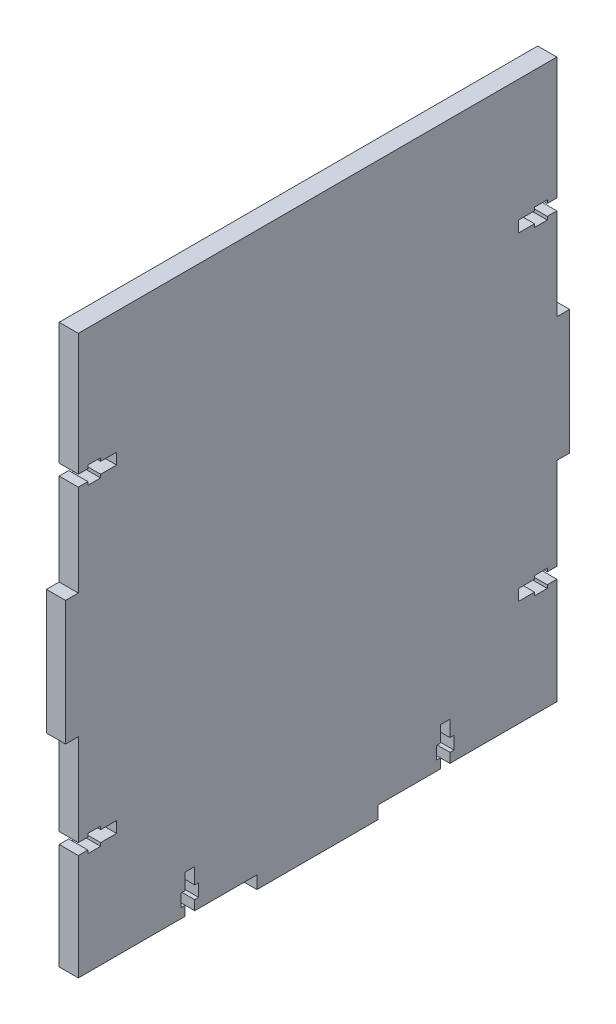
SolidWorks part; units mm, degrees
material "1060 Alloy"
ref_plane "Front Plane" through (0, 0, 0) normal (0, 0, 1) x (1, 0, 0)
ref_plane "Top Plane" through (0, 0, 0) normal (0, 1, 0) x (1, 0, 0)
ref_plane "Right Plane" through (0, 0, 0) normal (1, 0, 0) x (0, 0, -1)
sketch "Sketch1" plane through (0, 0, 0) normal (1, 0, 0) x (0, 0, -1)
  line L1 (-75, 0) -> (75, 0)
  line L2 (-75, 0) -> (-75, -175)
  line L3 (-75, -175) -> (75, -175)
  line L4 (75, 0) -> (75, -175)
  dimension "D1" = 150
  dimension "D2" = 175
sheet metal parameters "Sheet-Metal1" thickness 6 parameters "D1"=5
base flange "Base-Flange1" sketch "Sketch1" thickness 6 reverse thickness direction no parameters "D1"=5
sketch "Sketch4" plane through (0, 0, 0) normal (1, 0, 0) x (0, 0, -1)
  line L0 (-75, -38.25) -> (-75, -41.75)
  line L1 (-75, 0) -> (-75, -175) construction
  line L2 (-75, 0) -> (-75, -175) construction
  line L3 (-75, -41.75) -> (-72, -41.75)
  line L4 (-72, -41.75) -> (-72, -42.75)
  line L5 (-72, -42.75) -> (-68, -42.75)
  line L6 (-68, -42.75) -> (-68, -41.75)
  line L7 (-68, -41.75) -> (-63, -41.75)
  line L8 (-63, -41.75) -> (-63, -38.25)
  line L9 (-63, -38.25) -> (-68, -38.25)
  line L10 (-68, -38.25) -> (-68, -37.25)
  line L11 (-68, -37.25) -> (-72, -37.25)
  line L12 (-72, -37.25) -> (-72, -38.25)
  line L13 (-72, -38.25) -> (-75, -38.25)
  line L14 (-75, -90) -> (75, -90) construction
  line L15 (75, -175) -> (75, 0) construction
  line L16 (0, -90) -> (0, 0) construction
  line L17 (-75, -40) -> (-63, -40) construction
  line L18 (75, 0) -> (-75, 0) construction
  line L19 (-75, -140) -> (-63, -140) construction
  line L20 (-72, -141.75) -> (-75, -141.75)
  line L21 (-72, -142.75) -> (-72, -141.75)
  line L22 (-68, -142.75) -> (-72, -142.75)
  line L23 (-68, -141.75) -> (-68, -142.75)
  line L24 (-63, -141.75) -> (-68, -141.75)
  line L25 (-63, -138.25) -> (-63, -141.75)
  line L26 (-68, -138.25) -> (-63, -138.25)
  line L27 (-68, -137.25) -> (-68, -138.25)
  line L28 (-72, -137.25) -> (-68, -137.25)
  line L29 (-72, -138.25) -> (-72, -137.25)
  line L30 (-75, -138.25) -> (-72, -138.25)
  line L31 (-75, -141.75) -> (-75, -138.25)
  line L32 (75, -140) -> (63, -140) construction
  line L33 (75, -141.75) -> (75, -138.25)
  line L34 (75, -138.25) -> (72, -138.25)
  line L35 (72, -138.25) -> (72, -137.25)
  line L36 (72, -137.25) -> (68, -137.25)
  line L37 (68, -137.25) -> (68, -138.25)
  line L38 (68, -138.25) -> (63, -138.25)
  line L39 (63, -138.25) -> (63, -141.75)
  line L40 (63, -141.75) -> (68, -141.75)
  line L41 (68, -141.75) -> (68, -142.75)
  line L42 (68, -142.75) -> (72, -142.75)
  line L43 (72, -142.75) -> (72, -141.75)
  line L44 (72, -141.75) -> (75, -141.75)
  line L45 (75, -40) -> (63, -40) construction
  line L46 (72, -38.25) -> (75, -38.25)
  line L47 (72, -37.25) -> (72, -38.25)
  line L48 (68, -37.25) -> (72, -37.25)
  line L49 (68, -38.25) -> (68, -37.25)
  line L50 (63, -38.25) -> (68, -38.25)
  line L51 (63, -41.75) -> (63, -38.25)
  line L52 (68, -41.75) -> (63, -41.75)
  line L53 (68, -42.75) -> (68, -41.75)
  line L54 (72, -42.75) -> (68, -42.75)
  line L55 (72, -41.75) -> (72, -42.75)
  line L56 (75, -41.75) -> (72, -41.75)
  line L57 (75, -38.25) -> (75, -41.75)
  dimension "D1" = 3.5
  dimension "D2" = 5.5
  dimension "D3" = 4
  dimension "D4" = 3
  dimension "D5" = 5
  dimension "D6" = 40
  dimension "D7" = 100
extrude "Cut-Extrude1" cut sketch "Sketch4" against normal through all normal cut yes
sketch "Sketch5" plane through (0, 0, 0) normal (1, 0, 0) x (0, 0, -1)
  line L0 (-75, -38.25) -> (-75, -41.75) construction
  line L1 (-75, -138.25) -> (-75, -141.75) construction
  line L2 (-75, -140) -> (-75, -40) construction
  line L3 (-75, -90) -> (-79, -90) construction
  line L4 (0, 0) -> (0, -175) construction
  line L5 (-79, -70.5) -> (-75, -70.5)
  line L6 (-79, -70.5) -> (-79, -109.5)
  line L7 (-79, -109.5) -> (-75, -109.5)
  line L8 (-75, -70.5) -> (-75, -109.5)
  line L9 (-75, -175) -> (75, -175) construction
  line L10 (75, -90) -> (79, -90) construction
  line L11 (75, -140) -> (75, -40) construction
  line L12 (75, -138.25) -> (75, -141.75) construction
  line L13 (75, -38.25) -> (75, -41.75) construction
  line L14 (75, -70.5) -> (75, -109.5)
  line L15 (79, -109.5) -> (75, -109.5)
  line L16 (79, -70.5) -> (79, -109.5)
  line L17 (79, -70.5) -> (75, -70.5)
  line L19 (-19, -175) -> (19, -175)
  line L20 (-19, -175) -> (-19, -179)
  line L21 (-19, -179) -> (19, -179)
  line L22 (19, -175) -> (19, -179)
  dimension "D1" = 4
  dimension "D2" = 39
  dimension "D3" = 38
  dimension "D4" = 4
base flange "Tab1" sketch "Sketch5" thickness 6 reverse thickness direction no parameters "D1"=5
sketch "Sketch7" plane through (0, 0, 0) normal (1, 0, 0) x (0, 0, -1)
  line L0 (-41.5, -175) -> (-38.5, -175)
  line L1 (-75, -175) -> (-19, -175) construction
  line L2 (-38.5, -175) -> (-38.5, -172)
  line L3 (-38.5, -172) -> (-37.25, -172)
  line L4 (-37.25, -172) -> (-37.25, -168)
  line L5 (-37.25, -168) -> (-38.5, -168)
  line L6 (-38.5, -168) -> (-38.5, -163)
  line L7 (-38.5, -163) -> (-41.5, -163)
  line L8 (-41.5, -163) -> (-41.5, -168)
  line L9 (-41.5, -168) -> (-42.75, -168)
  line L10 (-42.75, -168) -> (-42.75, -172)
  line L11 (-42.75, -172) -> (-41.5, -172)
  line L12 (-41.5, -172) -> (-41.5, -175)
  line L13 (-40, -163) -> (-40, -175) construction
  line L14 (-41.5, -168) -> (-38.5, -168) construction
  line L15 (-41.5, -172) -> (-38.5, -172) construction
  line L16 (-41.5, -168) -> (-41.5, -172) construction
  line L17 (-38.5, -168) -> (-38.5, -172) construction
  line L18 (0, -179) -> (0, -183.2458) construction
  line L19 (-19, -179) -> (19, -179) construction
  line L20 (38.5, -168) -> (38.5, -172) construction
  line L21 (41.5, -168) -> (41.5, -172) construction
  line L22 (41.5, -172) -> (38.5, -172) construction
  line L23 (41.5, -168) -> (38.5, -168) construction
  line L24 (40, -163) -> (40, -175) construction
  line L25 (41.5, -172) -> (41.5, -175)
  line L26 (42.75, -172) -> (41.5, -172)
  line L27 (42.75, -168) -> (42.75, -172)
  line L28 (41.5, -168) -> (42.75, -168)
  line L29 (41.5, -163) -> (41.5, -168)
  line L30 (38.5, -163) -> (41.5, -163)
  line L31 (38.5, -168) -> (38.5, -163)
  line L32 (37.25, -168) -> (38.5, -168)
  line L33 (37.25, -172) -> (37.25, -168)
  line L34 (38.5, -172) -> (37.25, -172)
  line L35 (38.5, -175) -> (38.5, -172)
  line L36 (41.5, -175) -> (38.5, -175)
  dimension "D1" = 5.5
  dimension "D2" = 3
  dimension "D3" = 3
  dimension "D4" = 4
  dimension "D5" = 5
  dimension "D6" = 80
extrude "Cut-Extrude3" cut sketch "Sketch7" against normal through all normal cut yes
flat pattern "Flat-Pattern1" [suppressed]
sketch "Bend-Lines1" plane through (0, 0, 0) normal (0, 1, 0) x (1, 0, 0)
sketch3d "Bounding-Box1" [suppressed]
  line L0 (79, 0, 0) -> (79, -179, 0) construction
  line L1 (-79, 0, 0) -> (-79, -179, 0) construction
  line L2 (79, 0, 0) -> (-79, 0, 0) construction
  line L3 (79, -179, 0) -> (-79, -179, 0) construction
